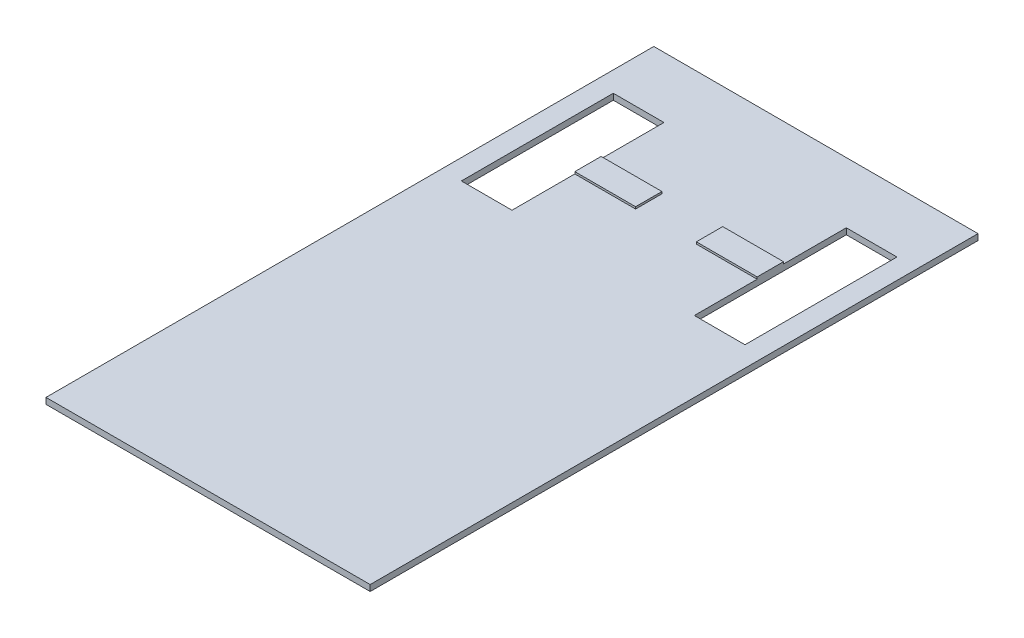
SolidWorks part; units mm, degrees
ref_plane "Front Plane" through (0, 0, 0) normal (0, 0, 1) x (1, 0, 0)
ref_plane "Top Plane" through (0, 0, 0) normal (0, 1, 0) x (1, 0, 0)
ref_plane "Right Plane" through (0, 0, 0) normal (1, 0, 0) x (0, 0, -1)
sketch "Sketch1" plane through (0, 0, 0) normal (0, 1, 0) x (1, 0, 0)
  line L0 (50.4858, -6.9084) -> (75.4858, -6.9084) construction
  line L1 (40.4858, 60.5916) -> (200.4858, 60.5916)
  line L2 (40.4858, 60.5916) -> (40.4858, -239.4084)
  line L3 (40.4858, -239.4084) -> (200.4858, -239.4084)
  line L4 (200.4858, 60.5916) -> (200.4858, -239.4084)
  line L5 (50.4858, 30.5916) -> (75.4858, 30.5916)
  line L6 (50.4858, 30.5916) -> (50.4858, -44.4084)
  line L7 (50.4858, -44.4084) -> (75.4858, -44.4084)
  line L8 (75.4858, 30.5916) -> (75.4858, -44.4084)
  line L9 (165.4858, 30.5916) -> (190.4858, 30.5916)
  line L10 (165.4858, 30.5916) -> (165.4858, -44.4084)
  line L11 (165.4858, -44.4084) -> (190.4858, -44.4084)
  line L12 (190.4858, 30.5916) -> (190.4858, -44.4084)
  line L13 (165.4858, -6.9084) -> (190.4858, -6.9084) construction
  line L14 (135.4858, -6.9084) -> (165.4858, -6.9084) construction
  line L15 (75.4858, -0.4084) -> (105.4858, -0.4084)
  line L16 (75.4858, -0.4084) -> (75.4858, -13.4084)
  line L17 (75.4858, -13.4084) -> (105.4858, -13.4084)
  line L18 (105.4858, -0.4084) -> (105.4858, -13.4084)
  line L19 (165.4858, -0.4084) -> (135.4858, -0.4084)
  line L20 (165.4858, -0.4084) -> (165.4858, -13.4084)
  line L21 (165.4858, -13.4084) -> (135.4858, -13.4084)
  line L22 (135.4858, -0.4084) -> (135.4858, -13.4084)
  line L23 (105.4858, -6.9084) -> (75.4858, -6.9084) construction
  line L24 (105.4858, -6.9084) -> (135.4858, -6.9084) construction
  dimension "D1" = 25
  dimension "D2" = 25
  dimension "D3" = 75
  dimension "D4" = 75
  dimension "D5" = 30
  dimension "D6" = 13
  dimension "D7" = 30
  dimension "D8" = 13
  dimension "D9" = 30
  dimension "D10" = 10
  dimension "D11" = 10
  dimension "D12" = 30
  dimension "D13" = 300
extrude "Boss-Extrude1" add sketch "Sketch1" along normal blind 3 contours L4 L1 L2 L3 L22 L19 L10 L9 L12 L11 L21 L15 L18 L17 L8 L7 L6 L5 region at (120.4858, 0, 98.0057)
extrude "Boss-Extrude2" add sketch "Sketch1<3>" along normal blind 4 contours L18 L15 L8 L17 | L19 L22 L21 L10 region at (90.4858, 0, 6.9084) region at (150.4858, 0, 6.9084)
sketch "Sketch1<3>" plane through (0, 0, 0) normal (0, 1, 0) x (1, 0, 0) same geometry as "Sketch1"
